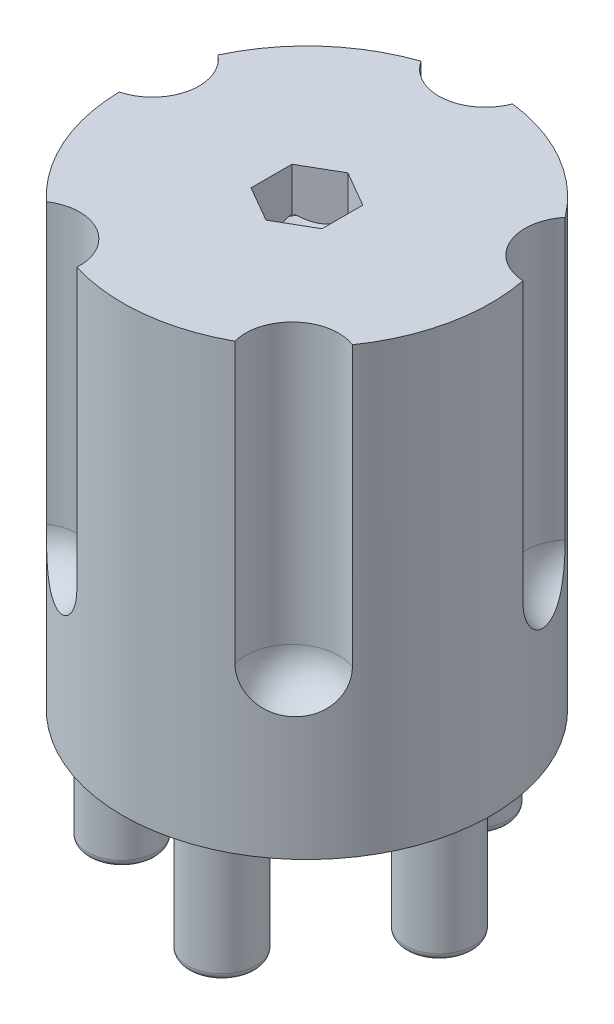
SolidWorks part; units mm, degrees
ref_plane "Front Plane" through (0, 0, 0) normal (0, 0, 1) x (1, 0, 0)
ref_plane "Top Plane" through (0, 0, 0) normal (0, 1, 0) x (1, 0, 0)
ref_plane "Right Plane" through (0, 0, 0) normal (1, 0, 0) x (0, 0, -1)
sketch "Sketch1" plane through (0, 0, 0) normal (0, 1, 0) x (1, 0, 0)
  circle A0 centre (0, 0) radius 25.75
  dimension "D1" = 51.5
extrude "Boss-Extrude1" add sketch "Sketch1" along normal blind 62
sketch "Sketch2" plane through (0, 0, 0) normal (0, -1, 0) x (1, 0, 0)
  circle A0 centre (0, 0) radius 18.5 construction
  circle A1 centre (18.5, 0) radius 4.75
  circle A2 centre (5.7168, -17.5945) radius 4.75
  circle A3 centre (-14.9668, -10.874) radius 4.75
  circle A4 centre (-14.9668, 10.874) radius 4.75
  circle A5 centre (5.7168, 17.5945) radius 4.75
  point P16 (0, 0)
  dimension "D2" = 9.5
  dimension "D3" = 37
  dimension "D1" = 5
extrude "Boss-Extrude2" add sketch "Sketch2" along normal blind 18
fillet "Fillet1" radius 1 5 edges at (5.7168, 0, 22.3445) (-14.9668, 0, 15.624) (-14.9668, 0, -6.124) (5.7168, 0, -12.8445) (18.5, 0, 4.75)
fillet "Fillet2" radius 1 5 edges at (-14.9668, -18, -15.624) (-14.9668, -18, 6.124) (5.7168, -18, 12.8445) (18.5, -18, -4.75) (5.7168, -18, -22.3445)
sketch "Sketch3" plane through (0, 62, 0) normal (0, 1, 0) x (1, 0, 0)
  line L1 (0, -5.7158) -> (4.95, -2.8579)
  line L2 (4.95, -2.8579) -> (4.95, 2.8579)
  line L3 (4.95, 2.8579) -> (0, 5.7158)
  line L4 (0, 5.7158) -> (-4.95, 2.8579)
  line L5 (-4.95, 2.8579) -> (-4.95, -2.8579)
  line L6 (-4.95, -2.8579) -> (0, -5.7158)
  circle A0 centre (0, 0) radius 4.95 construction
  dimension "D1" = 9.9
extrude "Cut-Extrude1" cut sketch "Sketch3" against normal blind 6.1
sketch "Sketch4" plane through (0, 0, 0) normal (0, -1, 0) x (1, 0, 0)
  circle A0 centre (0, 0) radius 10
  dimension "D1" = 20
extrude "Cut-Extrude2" cut sketch "Sketch4" against normal blind 45
sketch "Sketch5" plane through (0, 45, 0) normal (0, -1, 0) x (1, 0, 0)
  circle A0 centre (0, 0) radius 3
  dimension "D1" = 6
extrude "Cut-Extrude3" cut sketch "Sketch5" against normal through all
chamfer "Chamfer2" distance 2.5 distance2 3.4 1 edges at (0, 45, -3) first distance on face at (0, 45, -3)
sketch "Sketch6" plane through (0, 62, 0) normal (0, 1, 0) x (1, 0, 0)
  line L0 (-2.475, -4.2868) -> (-14, -24.2487) construction
  line L1 (-4.95, -2.8579) -> (0, -5.7158) construction
  circle A0 centre (0, 0) radius 28 construction
  circle A1 centre (-14, -24.2487) radius 6.5
  circle A2 centre (-27.3881, 5.8215) radius 6.5
  circle A3 centre (-2.9268, 27.8466) radius 6.5
  circle A4 centre (25.5793, 11.3886) radius 6.5
  circle A5 centre (18.7357, -20.8081) radius 6.5
  point P16 (0, 0)
  dimension "D2" = 13
  dimension "D3" = 56
  dimension "D1" = 5
extrude "Cut-Extrude4" cut sketch "Sketch6" against normal blind 45
fillet "Fillet3" radius 6 5 edges at (-10.75, 17, 18.6195) (-21.0302, 17, -4.4701) (-2.2474, 17, -21.3822) (19.6412, 17, -8.7448) (14.3863, 17, 15.9776)
chamfer "Chamfer3" distance 2.5 angle 45 1 edges at (0, 55.9, 3)
